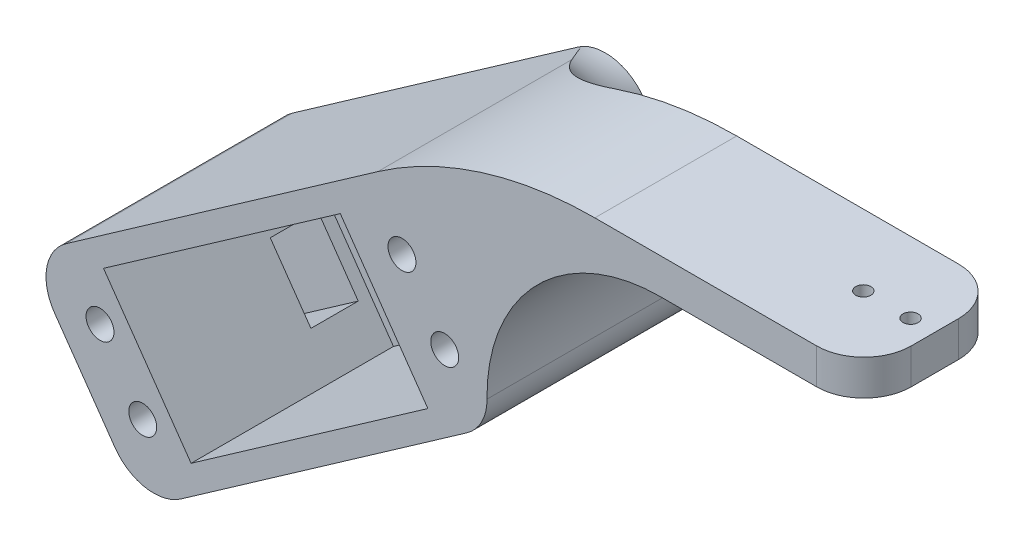
SolidWorks part; units mm, degrees
ref_plane "Front Plane" through (0, 0, 0) normal (0, 0, 1) x (1, 0, 0)
ref_plane "Top Plane" through (0, 0, 0) normal (0, 1, 0) x (1, 0, 0)
ref_plane "Right Plane" through (0, 0, 0) normal (1, 0, 0) x (0, 0, -1)
sketch "Sketch1" plane through (0, 0, 0) normal (0, 0, 1) x (1, 0, 0)
  line L0 (-5.8792, 8.3963) -> (-2.8679, 4.0958) construction
  line L1 (10.9135, 20.1546) -> (-22.6718, -3.362) construction
  line L2 (10.9135, 20.1546) -> (22.6718, 3.362) construction
  line L3 (22.6718, 3.362) -> (-10.9135, -20.1546) construction
  line L4 (-22.6718, -3.362) -> (-10.9135, -20.1546) construction
  line L5 (10.9135, 20.1546) -> (-10.9135, -20.1546) construction
  line L6 (22.6718, 3.362) -> (-22.6718, -3.362) construction
  line L7 (-23.1419, -10.1003) -> (17.4061, 18.2918) construction
  line L8 (-23.1419, -10.1003) -> (-17.4061, -18.2918) construction
  line L9 (-17.4061, -18.2918) -> (23.1419, 10.1003) construction
  line L10 (17.4061, 18.2918) -> (23.1419, 10.1003) construction
  line L11 (-20.274, -14.196) -> (-16.7926, -11.7583) construction
  line L12 (79.438, 35.4954) -> (43.3041, 35.4954)
  line L13 (14.1664, 26.3083) -> (-27.6876, -2.9981)
  line L14 (79.438, 35.4954) -> (79.438, 30.7329)
  line L15 (79.438, 30.7329) -> (52.1129, 30.7329)
  line L16 (26.1111, 1.8943) -> (-12.287, -24.9924)
  line L17 (-29.247, -11.842) -> (-21.1309, -23.433)
  circle A0 centre (-23.1419, -10.1003) radius 2.5 construction
  circle A1 centre (-17.4061, -18.2918) radius 2.5 construction
  circle A2 centre (17.4061, 18.2918) radius 2.5 construction
  circle A3 centre (23.1419, 10.1003) radius 2.5 construction
  arc A4 (14.1664, 26.3083) -> (43.3041, 35.4954) centre (43.3041, -15.3046) cw
  arc A5 (-21.1309, -23.433) -> (-12.287, -24.9924) centre (-15.9293, -19.7908) ccw
  arc A6 (-27.6876, -2.9981) -> (-29.247, -11.842) centre (-24.0454, -8.1998) ccw
  arc A7 (52.1129, 30.7329) -> (28.8184, 7.1689) centre (52.1129, 7.4369) ccw
  arc A8 (26.1111, 1.8943) -> (28.8184, 7.1689) centre (22.4689, 7.0959) ccw
  point P0 (0, 0)
  dimension "D3" = 49.5
  dimension "D5" = 35
  dimension "D7" = 50.8
  dimension "D9" = 5
  dimension "D11" = 3.175
  dimension "D12" = 6.35
  dimension "D1" = 20.5
  dimension "D2" = 41
  dimension "D4" = 10
  dimension "D6" = 3.175
  dimension "D8" = 3.175
  dimension "D10" = 6
  dimension "D13" = 4.7625
extrude "Boss-Extrude1" add sketch "Sketch1" along normal mid plane 19.05
fillet "Fillet1" radius 6.35 2 edges at (79.438, 33.1141, -9.525) (79.438, 33.1141, 9.525)
sketch "Sketch2" plane through (0, 0, 9.525) normal (0, 0, 1) x (1, 0, 0)
  line L0 (27.6705, 10.7381) -> (19.5544, 22.3291)
  line L1 (10.7105, 23.8885) -> (-27.6876, -2.9981)
  line L2 (-29.247, -11.842) -> (-21.1309, -23.433)
  line L3 (-12.287, -24.9924) -> (26.1111, 1.8943)
  line L4 (-29.247, -11.842) -> (-21.1309, -23.433) construction
  arc A0 (19.5544, 22.3291) -> (10.7105, 23.8885) centre (14.3527, 18.6869) ccw
  arc A1 (27.6705, 10.7381) -> (26.1111, 1.8943) centre (22.4689, 7.0959) cw
  arc A2 (-27.6876, -2.9981) -> (-29.247, -11.842) centre (-24.0454, -8.1998) ccw
  arc A3 (-21.1309, -23.433) -> (-12.287, -24.9924) centre (-15.9293, -19.7908) ccw
extrude "Boss-Extrude4" add sketch "Sketch2" against normal blind 30.353
fillet "Fillet4" radius 12.7 3 edges at (15.4554, 24.9404, -9.525) (28.5139, 9.0402, -9.525) (23.6124, 16.5336, -9.525) first distance on face at (37.4976, 25.7682, -9.525)
sketch "Sketch6" plane through (0, 0, 9.525) normal (0, 0, 1) x (1, 0, 0)
  line L4 (-22.6718, -3.362) -> (-10.9135, -20.1546)
  line L5 (-22.6718, -3.362) -> (9.1234, 18.9012)
  line L6 (-10.9135, -20.1546) -> (20.8817, 2.1086)
  line L7 (9.1234, 18.9012) -> (20.8817, 2.1086)
extrude "Cut-Extrude3" cut sketch "Sketch6" against normal blind 27.178
sketch "Sketch7" plane through (-25.1889, -17.6375, 0) normal (-0.8192, -0.5736, 0) x (0, 0, 1)
  line L0 (-16.0655, 13.425) -> (-16.0655, -13.425) construction
  line L1 (-16.0655, 4.7625) -> (-9.7155, 4.7625)
  line L2 (-16.0655, 4.7625) -> (-16.0655, -4.7625)
  line L3 (-16.0655, -4.7625) -> (-9.7155, -4.7625)
  line L4 (-9.7155, 4.7625) -> (-9.7155, -4.7625)
  line L5 (9.525, -13.425) -> (-20.828, -13.425) construction
  line L6 (9.525, 13.425) -> (-20.828, 13.425) construction
  line L7 (-20.828, 7.075) -> (-20.828, -7.075) construction
  point P9 (-16.0655, 0)
  dimension "D1" = 9.525
  dimension "D2" = 6.35
  dimension "D3" = 4.7625
extrude "Cut-Extrude4" cut sketch "Sketch7" against normal up to surface (10.25 mm away) up to face at (-16.7926, -11.7583, -4.064)
sketch "Sketch8" plane through (0, 0, 9.525) normal (0, 0, 1) x (1, 0, 0)
  circle A0 centre (17.4061, 18.2918) radius 1.875
  circle A1 centre (23.1419, 10.1003) radius 1.875
  circle A2 centre (-17.4061, -18.2918) radius 1.875
  circle A3 centre (-23.1419, -10.1003) radius 1.875
  dimension "D1" = 3.75
extrude "Cut-Extrude5" cut sketch "Sketch8" against normal blind 9.525
sketch "Sketch9" plane through (0, 35.4954, 0) normal (0, 1, 0) x (1, 0, 0)
  line L0 (79.438, 0) -> (52.1129, 0) construction
  line L1 (69.8221, 0) -> (72.9971, 0) construction
  line L2 (72.9971, 0) -> (76.1721, 0) construction
  line L3 (79.438, 0) -> (43.3041, 0) construction
  circle A0 centre (69.8221, 0) radius 1.016
  circle A1 centre (76.1721, 0) radius 1.016
  circle A2 centre (72.9971, 0) radius 1.016 construction
  dimension "D1" = 2.032
  dimension "D2" = 3.175
extrude "Cut-Extrude6" cut sketch "Sketch9" against normal up to surface (4.7625 mm away) up to face at (68.6513, 30.7329, 0)
